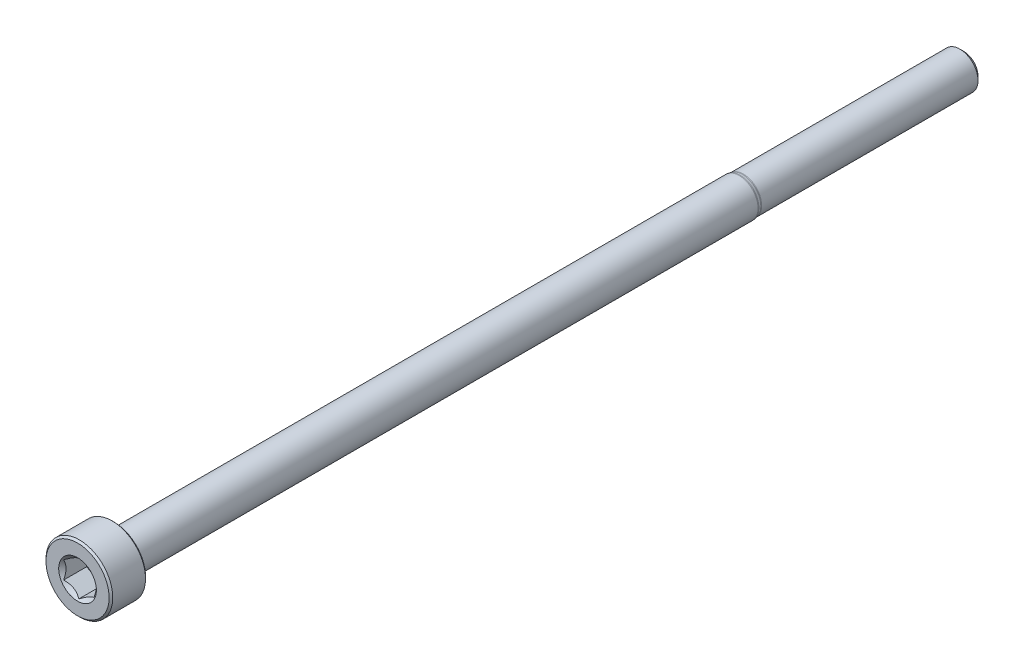
SolidWorks part; units mm, degrees
ref_plane "Front Plane" through (0, 0, 0) normal (0, 0, 1) x (1, 0, 0)
ref_plane "Top Plane" through (0, 0, 0) normal (0, 1, 0) x (1, 0, 0)
ref_plane "Right Plane" through (0, 0, 0) normal (1, 0, 0) x (0, 0, -1)
sketch "Sketch1" plane through (0, 0, 0) normal (1, 0, 0) x (0, 0, -1)
  line L0 (-36.5, 0) -> (36.5, 0) construction
  line L1 (36.5, 0) -> (36.5, 1.1752) construction
  line L2 (36.5, 1.1752) -> (36.1752, 1.5) construction
  line L3 (36.1752, 1.5) -> (36.125, 1.5) construction
  line L4 (36.125, 1.5) -> (-33.5, 1.5) construction
  line L5 (-33.5, 1.5) -> (-33.5, 2.75) construction
  line L6 (-33.5, 2.75) -> (-36.5, 2.75) construction
  line L7 (-36.5, 2.75) -> (-36.5, 0) construction
  line L8 (36.5, 1.1752) -> (36.5, 1.5) construction
  line L9 (36.4688, 1.5541) -> (36.7188, 1.1211) construction
  line L10 (36.7188, 1.1211) -> (36.9688, 1.5541) construction
  line L11 (36.9688, 1.5541) -> (36.4688, 1.5541) construction
  line L12 (36.7188, 1.5541) -> (36.7188, 1.5) construction
  line L13 (36.7188, 1.1211) -> (36.7188, 1.1752) construction
  line L14 (36.6875, 1.1752) -> (36.75, 1.1752) construction
  line L15 (36.5, 1.5) -> (36.9375, 1.5) construction
  line L16 (36.4844, 1.5271) -> (36.9531, 1.5271) construction
  line L17 (36.5, 0) -> (36.5, -1.5) construction
  line L18 (-33.65, 2.75) -> (-33.5, 2.6) construction
  line L19 (-36.35, 2.75) -> (-36.5, 2.6) construction
  line L20 (-33.5, 1.5) -> (-33.5, 0) construction
  line L21 (-33.5, 0.75) -> (-10.1667, 0.75) construction
  line L22 (-10.1667, 0.75) -> (13.1667, 0.75) construction
  line L23 (13.1667, 0.75) -> (36.5, 0.75) construction
  line L24 (-10.1667, 0.75) -> (-10.1667, 1.5) construction
  line L25 (-10.1667, 1.5) -> (-10.1667, 2.75) construction
  line L26 (13.1667, 0.75) -> (13.1667, 2.75) construction
  point P0 (-36.5, 1.25)
  point P3 (35.25, 1.5)
  point P4 (0, 0)
  point P18 (13.1667, 1.5)
  point P22 (36.7188, 1.1752)
  point P24 (36.125, 1.5)
  point P25 (36.7188, 1.5)
  point P28 (36.7188, 1.5271)
  point P29 (35.25, -1.5)
  point P30 (-10.1667, 1.5)
  point P31 (-35, 2.75)
  point P37 (-34.025, 2.75)
  point P38 (-36.275, 2.75)
  point P45 (-10.1667, 0.75)
  point P46 (13.1667, 0.75)
  point P49 (18.5, 1.5)
  dimension "D1" = 45
  dimension "D2" = 0.0625
  dimension "D7" = 0.15
  dimension "D8" = 0.15
  dimension "D9" = 0.15
  dimension "D10" = 0.075
  dimension "D11" = 0.375
  dimension "Drive Size" = 2.5
  dimension "Head Diameter" = 5.5
  dimension "Head Height" = 3
  dimension "Thread Pitch" = 0.5
  dimension "Thread Dia" = 3
  dimension "Length" = 70
  dimension "D12" = 0.375
  dimension "D4" = 1.25
  dimension "Minimum Thread Length" = 18
  dimension "D3" = 52
sketch "Sketch2" plane through (0, 0, 0) normal (1, 0, 0) x (0, 0, -1)
  line L0 (-36.5, 0) -> (-36.5, 2.6)
  line L1 (-36.35, 2.75) -> (-33.65, 2.75)
  line L2 (-33.5, 2.6) -> (-33.5, 1.7041)
  line L4 (36.1752, 1.5) -> (36.5, 1.1752)
  line L5 (36.5, 1.1752) -> (36.5, 0)
  line L6 (-33.5, 2.75) -> (-36.5, 2.75) construction
  line L7 (36.5, 0) -> (-36.5, 0)
  line L8 (-36.35, 2.75) -> (-36.5, 2.6) construction
  line L10 (-36.35, 2.75) -> (-36.5, 2.6)
  line L14 (-33.65, 2.75) -> (-33.5, 2.6) construction
  line L16 (-33.65, 2.75) -> (-33.5, 2.6)
  line L17 (-33.5, 1.5) -> (-33.5, 2.75) construction
  line L18 (-33.35, 1.5541) -> (18.0035, 1.5541)
  line L19 (18.3494, 1.5) -> (36.1752, 1.5)
  line L20 (36.125, 1.5) -> (-33.5, 1.5) construction
  line L21 (18.0766, 1.5469) -> (18.2763, 1.5072)
  line L22 (36.9688, 1.5541) -> (36.4688, 1.5541) construction
  arc A1 (-33.5, 1.7041) -> (-33.35, 1.5541) centre (-33.35, 1.7041) ccw
  arc A2 (18.0035, 1.5541) -> (18.0766, 1.5469) centre (18.0035, 1.1791) cw
  arc A3 (18.2763, 1.5072) -> (18.3494, 1.5) centre (18.3494, 1.875) ccw
  point P39 (18.3125, 1.5)
  dimension "D3" = 0.15
  dimension "D6" = 0.375
  dimension "D4" = 11.25
  dimension "D5" = 0.1875
revolve "Revolve1" add sketch "Sketch2" angle 360 about L7
sketch "Sketch3" plane through (0, 0, 36.5) normal (0, 0, 1) x (1, 0, 0)
  line L1 (1.25, -0.7217) -> (1.25, 0.7217)
  line L2 (1.25, 0.7217) -> (0, 1.4434)
  line L3 (0, 1.4434) -> (-1.25, 0.7217)
  line L4 (-1.25, 0.7217) -> (-1.25, -0.7217)
  line L5 (-1.25, -0.7217) -> (0, -1.4434)
  line L6 (0, -1.4434) -> (1.25, -0.7217)
  circle A0 centre (0, 0) radius 1.25 construction
  circle A1 centre (0, 0) radius 2.75 construction
  circle A2 centre (0, 0) radius 2.75 construction
  circle A3 centre (0, 0) radius 1.4434 construction
  dimension "D1" = 2.8868
extrude "Cut-Extrude1" cut sketch "Sketch3" against normal offset from surface (2 mm away) 1 up to face at (0, 2.6, 33.5)
sketch "Sketch4" plane through (0, 0, 36.5) normal (0, 0, 1) x (1, 0, 0)
  circle A0 centre (0, 0) radius 1.5516
  dimension "D1" = 3.1033
extrude "Cut-Extrude2" cut sketch "Sketch4" against normal up to vertex (1.5 mm away) draft 45 up to point (0, 2.75, 35)
sketch "Sketch11" plane through (0, 0, 0) normal (1, 0, 0) x (0, 0, -1)
  line L0 (-36.5, 0) -> (36.5, 0) construction
  line L1 (-36.5, 0) -> (36.5, 0) construction
  line L2 (-28.95, 0) -> (-28.95, 1.5) construction
  line L3 (36.125, 1.5) -> (-33.5, 1.5) construction
  line L4 (13.4535, 0) -> (13.4535, 1.5) construction
  point P2 (-28.95, 0)
  point P3 (13.4535, 0)
  dimension "D1" = 4.55
  dimension "D2" = 4.55
sketch "Sketch6" [suppressed] plane through (0, 0, -36.5) normal (0, 0, -1) x (-1, 0, 0)
  circle A0 centre (0, 0) radius 1.5
curve "Helix/Spiral1" [suppressed] pitch 0.5 height 18.5 turns 37
sketch "Sketch10" [suppressed] plane through (0, 0, 0) normal (1, 0, 0) x (0, 0, -1)
  line L0 (18.5, -1.5) -> (18.5, 1.5)
  line L2 (-36.5, 0) -> (36.5, 0) construction
  point P3 (18.5, 0)
split "Split1" [suppressed] bodies to split 106
sketch "Sketch7" [suppressed] plane through (0, 0, 0) normal (1, 0, 0) x (0, 0, -1)
  line L0 (36.4844, 1.5271) -> (36.9531, 1.5271)
  line L1 (36.9531, 1.5271) -> (36.75, 1.1752)
  line L2 (36.75, 1.1752) -> (36.6875, 1.1752)
  line L3 (36.6875, 1.1752) -> (36.4844, 1.5271)
sweep "Cut-Sweep1" [suppressed] cut profiles "Sketch7" path "Helix/Spiral1"
sketch "Sketch8" [suppressed] plane through (0, 0, 0) normal (1, 0, 0) x (0, 0, -1)
  line L0 (-33.5, 0) -> (-33.5, 1.5)
  line L2 (-33.5, 1.5) -> (18.5, 1.5)
  line L4 (18.5, 1.5) -> (19.366, 0)
  line L5 (19.366, 0) -> (-33.5, 0)
  line L6 (36.125, 1.5) -> (-33.5, 1.5) construction
  line L7 (-36.5, 0) -> (36.5, 0) construction
  dimension "D1" = 60
  dimension "D2" = 18
revolve "Revolve2" [suppressed] add sketch "Sketch8" angle 360 about L5
sketch "Sketch12" plane through (0, 0, -36.5) normal (0, 0, -1) x (-1, 0, 0)
  circle A0 centre (0, 0) radius 1.5
  circle A1 centre (0, 0) radius 1.5 construction
extrude "Cut-Extrude3" [suppressed] cut sketch "Sketch12" against normal blind 10
equation "\"D2@Sketch1\" = \"Thread Pitch@Sketch1\" / 8"
equation "\"D4@Helix/Spiral1\" = \"Thread Pitch@Sketch1\""
equation "\"D7@Sketch1\" = \"Head Height@Sketch1\" * .05"
equation "\"D8@Sketch1\"=\"D7@Sketch1\""
equation "\"D9@Sketch1\"=\"D7@Sketch1\""
equation "\"D10@Sketch1\"=\"D7@Sketch1\"/2"
equation "\"D11@Sketch1\"=\"D10@Sketch1\"*5"
equation "\"D4@Sketch1\"=\"Thread Pitch@Sketch1\"*2.5"
equation "\"D12@Sketch1\"=\"Thread Pitch@Sketch1\"*.75"
equation "\"D3@Helix/Spiral1\"=\"Minimum Thread Length@Sketch1\"+\"Thread Pitch@Sketch1\""
equation "\"D2@Sketch8\"=\"Minimum Thread Length@Sketch1\""
equation "\"D3@Sketch2\"=\"Thread Dia@Sketch1\"*0.05"
equation "\"D5@Sketch2\"=\"D12@Sketch1\"*0.5"
equation "\"D6@Sketch2\"=\"Thread Dia@Sketch1\"*0.125"
equation "\"D1@Sketch11\"=\"D3@Sketch1\"*0.0875"
equation "\"D2@Sketch11\"=\"D1@Sketch11\""
equation "\"D1@Sketch4\"=\"D1@Sketch3\"*1.075"
